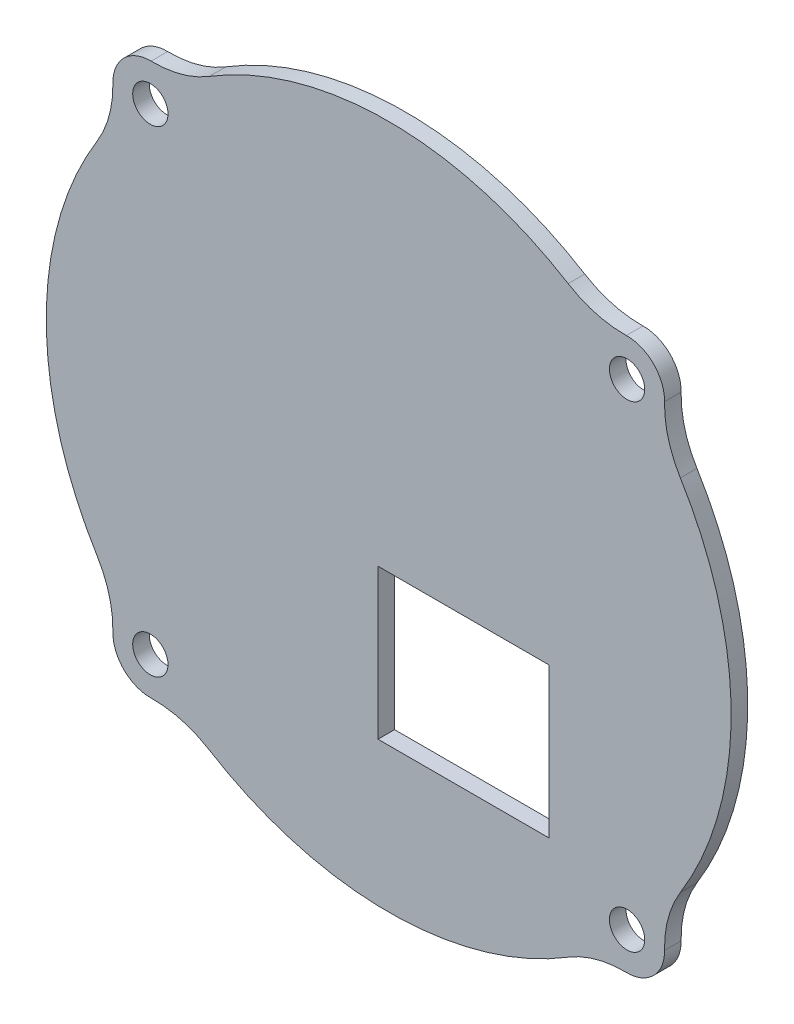
SolidWorks part; units mm, degrees
ref_plane "Plan de face" through (0, 0, 0) normal (0, 0, 1) x (1, 0, 0)
ref_plane "Plan de dessus" through (0, 0, 0) normal (0, 1, 0) x (1, 0, 0)
ref_plane "Plan de droite" through (0, 0, 0) normal (1, 0, 0) x (0, 0, -1)
sketch "Esquisse1" plane through (0, 0, 0) normal (0, 0, 1) x (1, 0, 0)
  line L0 (0, 31.5) -> (0, 0) construction
  line L1 (15.5, 21) -> (-15.5, 21) construction
  line L2 (15.5, 21) -> (15.5, -21) construction
  line L3 (15.5, -21) -> (-15.5, -21) construction
  line L4 (-15.5, 21) -> (-15.5, -21) construction
  line L5 (15.5, 21) -> (-15.5, -21) construction
  line L6 (15.5, -21) -> (-15.5, 21) construction
  line L7 (0, 0) -> (-22.2739, 22.2739) construction
  arc A0 (-24.9579, 20.0276) -> (-24.9579, -20.0276) centre (0, 0) ccw
  circle A1 centre (0, 0) radius 31.5 construction
  circle A2 centre (-22.2739, 22.2739) radius 1.65
  circle A3 centre (22.2739, 22.2739) radius 1.65
  circle A4 centre (22.2739, -22.2739) radius 1.65
  circle A5 centre (-22.2739, -22.2739) radius 1.65
  arc A6 (-20.0276, 24.9579) -> (-24.9579, 20.0276) centre (-22.2739, 22.2739) ccw
  arc A7 (24.9579, 20.0276) -> (20.0276, 24.9579) centre (22.2739, 22.2739) ccw
  arc A8 (20.0276, -24.9579) -> (24.9579, -20.0276) centre (22.2739, -22.2739) ccw
  arc A9 (-24.9579, -20.0276) -> (-20.0276, -24.9579) centre (-22.2739, -22.2739) ccw
  arc A10 (20.0276, 24.9579) -> (-20.0276, 24.9579) centre (0, 0) ccw
  arc A11 (24.9579, -20.0276) -> (24.9579, 20.0276) centre (0, 0) ccw
  arc A13 (-20.0276, -24.9579) -> (20.0276, -24.9579) centre (0, 0) ccw
  point P0 (0, 0)
  point P21 (0, 0)
  point P29 (0, 0)
  dimension "D3" = 63
  dimension "D5" = 3.3
  dimension "D7" = 64
  dimension "D9" = 7
  dimension "D1" = 31
  dimension "D2" = 42
  dimension "D4" = 45
  dimension "D6" = 4
  dimension "D8" = 4
extrude "Boss.-Extru.1" add sketch "Esquisse1" along normal blind 1.55
sketch "Esquisse2" plane through (0, 0, 1.55) normal (0, 0, 1) x (1, 0, 0)
  line L1 (15, 20.5) -> (-15, 20.5) construction
  line L2 (15, 20.5) -> (15, -20.5) construction
  line L3 (15, -20.5) -> (-15, -20.5) construction
  line L4 (-15, 20.5) -> (-15, -20.5) construction
  line L5 (15, 20.5) -> (-15, -20.5) construction
  line L6 (15, -20.5) -> (-15, 20.5) construction
  point P0 (0, 0)
  dimension "D1" = 30
  dimension "D2" = 41
sketch "Esquisse3" plane through (0, 0, 1.55) normal (0, 0, 1) x (1, 0, 0)
  line L0 (15, 20.5) -> (-15, 20.5) construction
  line L1 (15, 20.5) -> (15, -20.5) construction
  line L2 (-15, 20.5) -> (-15, -20.5) construction
  line L3 (15, -20.5) -> (-15, -20.5) construction
  line L4 (15, 20.5) -> (-15, 20.5) construction
  line L5 (15, 20.5) -> (15, -20.5) construction
  line L6 (-15, 20.5) -> (-15, -20.5) construction
  line L7 (15, -20.5) -> (-15, -20.5) construction
  line L9 (-1, -18.5) -> (13, -18.5)
  line L10 (-1, -18.5) -> (-1, -10.5)
  line L11 (-1, -10.5) -> (13, -10.5)
  line L12 (13, -18.5) -> (13, -10.5)
  line L13 (-1, -18.5) -> (13, -10.5) construction
  line L14 (-1, -10.5) -> (13, -18.5) construction
  point P2 (6, -14.5)
  dimension "D1" = 4
  dimension "D2" = 4
  dimension "D3" = 16
  dimension "D4" = 20
extrude "Enlèv. mat.-Extru.1" cut sketch "Esquisse3" against normal through all
sketch "Esquisse4" plane through (0, 0, 1.55) normal (0, 0, 1) x (1, 0, 0)
  line L1 (15, -4.5) -> (-1, -4.5)
  line L2 (15, -4.5) -> (15, -12.5)
  line L3 (15, -12.5) -> (-1, -12.5)
  line L4 (-1, -4.5) -> (-1, -12.5)
  line L5 (15, -20.5) -> (-15, -20.5) construction
  line L6 (15, 20.5) -> (15, -20.5) construction
  point P4 (15, -2.4497)
  point P8 (0, 0)
  point P9 (0, 0)
  dimension "D1" = 8
  dimension "D2" = 16
  dimension "D3" = 16
extrude "Enlèv. mat.-Extru.2" cut sketch "Esquisse4" against normal blind 1.55
sketch "Esquisse5" plane through (0, 0, 1.55) normal (0, 0, 1) x (1, 0, 0)
  line L0 (15, 20.5) -> (15, -20.5) construction
  line L1 (13, -12.5) -> (15, -12.5)
  line L2 (13, -12.5) -> (13, -18.5)
  line L3 (13, -18.5) -> (15, -18.5)
  line L4 (15, -12.5) -> (15, -18.5)
  line L5 (13, -18.5) -> (13, -12.5) construction
  point P7 (13, -18.5)
extrude "Enlèv. mat.-Extru.3" cut sketch "Esquisse5" against normal blind 1.55
fillet "Congé1" radius 10 8 edges at (24.9579, -20.0276, 0.775) (20.0276, -24.9579, 0.775) (-20.0276, -24.9579, 0.775) (-24.9579, -20.0276, 0.775) (-24.9579, 20.0276, 0.775) (-20.0276, 24.9579, 0.775) (20.0276, 24.9579, 0.775) (24.9579, 20.0276, 0.775)
